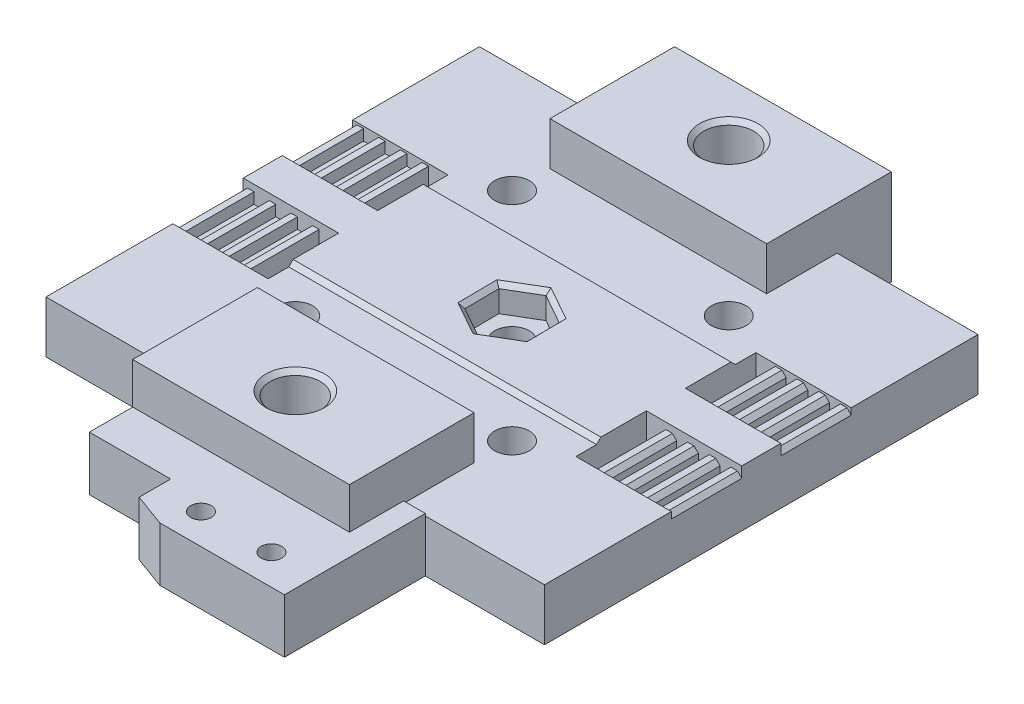
SolidWorks part; units mm, degrees
ref_plane "前视基准面" through (0, 0, 0) normal (0, 0, 1) x (1, 0, 0)
ref_plane "上视基准面" through (0, 0, 0) normal (0, 1, 0) x (1, 0, 0)
ref_plane "右视基准面" through (0, 0, 0) normal (1, 0, 0) x (0, 0, -1)
other "Configuration Table"
sketch "草图1" plane through (0, 0, 0) normal (0, 1, 0) x (1, 0, 0)
  line L1 (0, 0) -> (40, 0)
  line L2 (0, 0) -> (0, -40)
  line L3 (0, -40) -> (40, -40)
  line L4 (40, 0) -> (40, -40)
  dimension "D1" = 40
  dimension "40" = 40
extrude "凸台-拉伸1" add sketch "草图1" along normal blind 4.8
sketch "草图2" plane through (0, 4.8, 0) normal (0, 1, 0) x (1, 0, 0)
  line L0 (0, -40) -> (40, -40) construction
  line L1 (0, 0) -> (0, -40) construction
  circle A0 centre (10, -30) radius 1.6
  circle A1 centre (30, -30) radius 1.6
  circle A2 centre (30, -10) radius 1.6
  circle A3 centre (10, -10) radius 1.6
  dimension "D1" = 3.2
  dimension "D4" = 10
  dimension "D5" = 10
  dimension "D2" = 2
  dimension "D3" = 2
extrude "切除-拉伸1" cut sketch "草图2" against normal through all
sketch "草图3" plane through (0, 4.8, 0) normal (0, 1, 0) x (1, 0, 0)
  line L0 (0, 0) -> (0, -40) construction
  line L1 (0, -13.6) -> (40, -13.6)
  line L2 (0, -13.6) -> (0, -26.4)
  line L3 (0, -26.4) -> (40, -26.4)
  line L4 (40, -13.6) -> (40, -26.4)
  line L5 (40, -40) -> (40, 0) construction
  line L6 (40, 0) -> (0, 0) construction
  dimension "D1" = 12.8
  dimension "D2" = 13.6
extrude "凸台-拉伸2" add sketch "草图3" along normal blind 0.4
chamfer "倒角1" distance 0.4 angle 45 2 edges at (20, 5.2, 26.4) (20, 5.2, 13.6)
sketch "草图4" plane through (0, 0, 0) normal (0, -1, 0) x (1, 0, 0)
  line L0 (0, 40) -> (40, 40) construction
  line L1 (10, 40) -> (30, 40)
  line L2 (10, 40) -> (10, 45)
  line L3 (10, 45) -> (30, 45)
  line L4 (30, 40) -> (30, 45)
  line L5 (40, 0) -> (0, 0) construction
  line L6 (10, 0) -> (30, 0)
  line L7 (10, 0) -> (10, -5)
  line L8 (10, -5) -> (30, -5)
  line L9 (30, 0) -> (30, -5)
  line L10 (40, 40) -> (40, 0) construction
  point P12 (20, 0)
  point P15 (20, 40)
  dimension "D1" = 20
  dimension "D2" = 20
  dimension "D3" = 20
  dimension "D4" = 20
  dimension "D5" = 5
  dimension "D6" = 5
extrude "凸台-拉伸3" add sketch "草图4" against normal blind 4.8
sketch "草图5" plane through (0, 0, 0) normal (0, -1, 0) x (-1, 0, 0)
  line L0 (0, 0) -> (0, -40) construction
  line L1 (-30, -40) -> (-40, -40) construction
  circle A0 centre (-20, -20) radius 1.6
  circle A1 centre (-20, 0) radius 1.6
  circle A2 centre (-20, -40) radius 1.6
  dimension "D1" = 3.2
  dimension "D2" = 3.2
  dimension "D3" = 3.2
  dimension "D4" = 20
  dimension "D5" = 20
  dimension "D6" = 20
  dimension "D7" = 20
  dimension "D8" = 20
  dimension "D9" = 20
extrude "切除-拉伸2" cut sketch "草图5" against normal through all
sketch "草图6" plane through (0, 0, 0) normal (0, -1, 0) x (-1, 0, 0)
  line L0 (-30, -45) -> (-10, -45) construction
  line L1 (-15.5, -45) -> (-24.5, -45)
  line L2 (-15.5, -45) -> (-15.5, 5)
  line L3 (-15.5, 5) -> (-24.5, 5)
  line L4 (-24.5, -45) -> (-24.5, 5)
  line L5 (-10, 5) -> (-30, 5) construction
  line L6 (-30, -40) -> (-30, -45) construction
  point P8 (-20, -45)
  dimension "D1" = 9
  dimension "D2" = 10
extrude "切除-拉伸4" cut sketch "草图6" against normal blind 0.8
sketch "草图7" plane through (0, 4.8, 0) normal (0, 1, 0) x (1, 0, 0)
  line L0 (0, 0) -> (0, -13.6) construction
  line L1 (0, -6.5) -> (40, -6.5) construction
  line L2 (0, -6.5) -> (0, -33.5) construction
  line L3 (0, -33.5) -> (40, -33.5) construction
  line L4 (40, -6.5) -> (40, -33.5) construction
  line L5 (40, -40) -> (40, -26.4) construction
  line L6 (0, -40) -> (10, -40) construction
  line L8 (10, 5) -> (30, 5)
  line L9 (10, 5) -> (10, -6.5)
  line L10 (10, -6.5) -> (30, -6.5)
  line L11 (30, 5) -> (30, -6.5)
  line L12 (10, -45) -> (30, -45)
  line L13 (10, -45) -> (10, -33.5)
  line L14 (10, -33.5) -> (30, -33.5)
  line L15 (30, -45) -> (30, -33.5)
  circle A0 centre (20, 0) radius 1.6
  circle A1 centre (20, -40) radius 1.6
  point P8 (0, -20)
  dimension "D1" = 27
  dimension "D2" = 20
extrude "凸台-拉伸4" add sketch "草图7" along normal blind 4
sketch "草图8" plane through (0, 8.8, 0) normal (0, 1, 0) x (1, 0, 0)
  circle A0 centre (20, 0) radius 2.3
  circle A1 centre (20, -40) radius 2.3
  dimension "D1" = 4.6
  dimension "D2" = 4.6
extrude "切除-拉伸5" cut sketch "草图8" against normal blind 4.4
chamfer "倒角2" distance 0.4 angle 45 2 edges at (20, 8.8, 42.3) (20, 8.8, 2.3)
sketch "草图9" plane through (0, 5.2, 0) normal (0, 1, 0) x (1, 0, 0)
  line L1 (22.7676, -21.5568) -> (22.732, -18.3816)
  line L2 (22.732, -18.3816) -> (19.9644, -16.8248)
  line L3 (19.9644, -16.8248) -> (17.2324, -18.4432)
  line L4 (17.2324, -18.4432) -> (17.268, -21.6184)
  line L5 (17.268, -21.6184) -> (20.0356, -23.1752)
  line L6 (20.0356, -23.1752) -> (22.7676, -21.5568)
  circle A0 centre (20, -20) radius 2.75 construction
  dimension "D1" = 5.5
extrude "切除-拉伸6" cut sketch "草图9" against normal blind 2.4
chamfer "倒角3" distance 0.4 angle 45 6 edges at (21.3482, 5.2, 17.6032) (22.7498, 5.2, 19.9692) (21.4016, 5.2, 22.366) (18.6518, 5.2, 22.3968) (17.2502, 5.2, 20.0308) (18.5984, 5.2, 17.634)
sketch "草图10" plane through (40, 0, 0) normal (1, 0, 0) x (0, 0, -1)
  line L16 (-14, 5.2) -> (-26, 5.2)
  line L17 (-26, 5.2) -> (-26.4, 4.8)
  line L18 (-26.4, 4.8) -> (-40, 4.8)
  line L19 (-40, 4.8) -> (-40, 0)
  line L20 (-40, 0) -> (0, 0)
  line L21 (0, 0) -> (0, 4.8)
  line L22 (0, 4.8) -> (-13.6, 4.8)
  line L23 (-13.6, 4.8) -> (-14, 5.2)
  line L24 (-14, 5.2) -> (-26, 5.2)
  line L25 (-26, 5.2) -> (-26.4, 4.8)
  line L26 (-26.4, 4.8) -> (-40, 4.8)
  line L27 (-40, 4.8) -> (-40, 0)
  line L28 (-40, 0) -> (0, 0)
  line L29 (0, 0) -> (0, 4.8)
  line L30 (0, 4.8) -> (-13.6, 4.8)
  line L31 (-13.6, 4.8) -> (-14, 5.2)
  dimension "D1" = 0
extrude "凸台-拉伸5" add sketch "草图10" along normal blind 3
sketch "草图11" plane through (0, 0, 0) normal (-1, 0, 0) x (0, 0, 1)
  line L16 (40, 4.8) -> (26.4, 4.8)
  line L17 (26.4, 4.8) -> (26, 5.2)
  line L18 (26, 5.2) -> (14, 5.2)
  line L19 (14, 5.2) -> (13.6, 4.8)
  line L20 (13.6, 4.8) -> (0, 4.8)
  line L21 (0, 4.8) -> (0, 0)
  line L22 (0, 0) -> (40, 0)
  line L23 (40, 0) -> (40, 4.8)
  line L24 (40, 4.8) -> (26.4, 4.8)
  line L25 (26.4, 4.8) -> (26, 5.2)
  line L26 (26, 5.2) -> (14, 5.2)
  line L27 (14, 5.2) -> (13.6, 4.8)
  line L28 (13.6, 4.8) -> (0, 4.8)
  line L29 (0, 4.8) -> (0, 0)
  line L30 (0, 0) -> (40, 0)
  line L31 (40, 0) -> (40, 4.8)
  dimension "D1" = 0
extrude "凸台-拉伸6" add sketch "草图11" along normal blind 3
sketch "草图12" plane through (0, 0, 0) normal (0, -1, 0) x (-1, 0, 0)
  line L0 (3, 0) -> (3, -40) construction
  line L1 (3, -28.3) -> (-6.3, -28.3) construction
  line L2 (3, -28.3) -> (3, -21.8) construction
  line L3 (3, -21.8) -> (-6.3, -21.8) construction
  line L4 (-6.3, -28.3) -> (-6.3, -21.8) construction
  line L5 (0, -28.3) -> (0, -21.8)
  line L6 (3, -18.2) -> (-6.3, -18.2) construction
  line L7 (3, -18.2) -> (3, -11.7) construction
  line L8 (3, -11.7) -> (-6.3, -11.7) construction
  line L9 (-6.3, -18.2) -> (-6.3, -11.7) construction
  line L10 (3, -40) -> (-10, -40) construction
  line L11 (0, -28.3) -> (-1, -28.3)
  line L12 (-20, -45) -> (-20, -4.7094) construction
  line L13 (-24.5, 5) -> (-24.5, -45) construction
  line L14 (-1, -28.3) -> (-1, -21.8)
  line L15 (-43, -11.7) -> (-33.7, -11.7) construction
  line L16 (-33.7, -18.2) -> (-33.7, -11.7) construction
  line L17 (-43, -18.2) -> (-43, -11.7) construction
  line L18 (-43, -28.3) -> (-43, -21.8) construction
  line L19 (-43, -21.8) -> (-33.7, -21.8) construction
  line L20 (-33.7, -28.3) -> (-33.7, -21.8) construction
  line L21 (-43, -28.3) -> (-33.7, -28.3) construction
  line L22 (-33.7, -18.2) -> (-43, -18.2) construction
  line L23 (0, -21.8) -> (-1, -21.8)
  line L24 (2, -28.3) -> (1, -28.3)
  line L25 (2, -28.3) -> (2, -21.8)
  line L26 (2, -21.8) -> (1, -21.8)
  line L27 (1, -28.3) -> (1, -21.8)
  line L28 (-2, -28.3) -> (-2, -21.8)
  line L29 (-2, -28.3) -> (-3, -28.3)
  line L30 (-3, -28.3) -> (-3, -21.8)
  line L31 (-2, -21.8) -> (-3, -21.8)
  line L32 (-4, -28.3) -> (-4, -21.8)
  line L33 (-4, -28.3) -> (-5, -28.3)
  line L34 (-5, -28.3) -> (-5, -21.8)
  line L35 (-4, -21.8) -> (-5, -21.8)
  line L36 (3, -20) -> (-12.765, -20) construction
  line L37 (-4, -11.7) -> (-5, -11.7)
  line L38 (-5, -11.7) -> (-5, -18.2)
  line L39 (-4, -18.2) -> (-5, -18.2)
  line L40 (-4, -11.7) -> (-4, -18.2)
  line L41 (-2, -11.7) -> (-3, -11.7)
  line L42 (-3, -11.7) -> (-3, -18.2)
  line L43 (-2, -18.2) -> (-3, -18.2)
  line L44 (-2, -11.7) -> (-2, -18.2)
  line L45 (0, -11.7) -> (-1, -11.7)
  line L46 (-1, -11.7) -> (-1, -18.2)
  line L47 (0, -18.2) -> (-1, -18.2)
  line L48 (0, -11.7) -> (0, -18.2)
  line L49 (2, -18.2) -> (1, -18.2)
  line L50 (1, -11.7) -> (1, -18.2)
  line L51 (2, -11.7) -> (1, -11.7)
  line L52 (2, -11.7) -> (2, -18.2)
  line L53 (-36, -11.7) -> (-36, -18.2)
  line L54 (-36, -18.2) -> (-35, -18.2)
  line L55 (-35, -11.7) -> (-35, -18.2)
  line L56 (-36, -11.7) -> (-35, -11.7)
  line L57 (-38, -11.7) -> (-38, -18.2)
  line L58 (-38, -18.2) -> (-37, -18.2)
  line L59 (-37, -11.7) -> (-37, -18.2)
  line L60 (-38, -11.7) -> (-37, -11.7)
  line L61 (-40, -11.7) -> (-40, -18.2)
  line L62 (-40, -18.2) -> (-39, -18.2)
  line L63 (-39, -11.7) -> (-39, -18.2)
  line L64 (-40, -11.7) -> (-39, -11.7)
  line L65 (-42, -11.7) -> (-42, -18.2)
  line L66 (-42, -11.7) -> (-41, -11.7)
  line L67 (-41, -11.7) -> (-41, -18.2)
  line L68 (-42, -18.2) -> (-41, -18.2)
  line L69 (-36, -28.3) -> (-35, -28.3)
  line L70 (-35, -28.3) -> (-35, -21.8)
  line L71 (-36, -21.8) -> (-35, -21.8)
  line L72 (-36, -28.3) -> (-36, -21.8)
  line L73 (-38, -28.3) -> (-37, -28.3)
  line L74 (-37, -28.3) -> (-37, -21.8)
  line L75 (-38, -21.8) -> (-37, -21.8)
  line L76 (-38, -28.3) -> (-38, -21.8)
  line L77 (-40, -28.3) -> (-39, -28.3)
  line L78 (-39, -28.3) -> (-39, -21.8)
  line L79 (-40, -21.8) -> (-39, -21.8)
  line L80 (-40, -28.3) -> (-40, -21.8)
  line L81 (-42, -21.8) -> (-41, -21.8)
  line L82 (-41, -28.3) -> (-41, -21.8)
  line L83 (-42, -28.3) -> (-41, -28.3)
  line L84 (-42, -28.3) -> (-42, -21.8)
  dimension "D1" = 6.5
  dimension "D2" = 3.6
  dimension "D3" = 6.5
  dimension "D4" = 9.3
  dimension "D5" = 9.3
  dimension "D6" = 11.7
  dimension "D7" = 4.5
  dimension "D8" = 1
  dimension "D9" = 1
  dimension "D10" = 4
extrude "切除-拉伸7" cut sketch "草图12" against normal blind 1
sketch "草图13" plane through (0, 0, 0) normal (0, -1, 0) x (-1, 0, 0)
  line L1 (-4, -28.3) -> (-5.8, -28.3)
  line L2 (-4, -28.3) -> (-4, -21.8)
  line L3 (-4, -21.8) -> (-5.8, -21.8)
  line L4 (-5.8, -28.3) -> (-5.8, -21.8)
  line L5 (-4, -18.2) -> (-5.8, -18.2)
  line L6 (-4, -18.2) -> (-4, -11.7)
  line L7 (-4, -11.7) -> (-5.8, -11.7)
  line L8 (-5.8, -18.2) -> (-5.8, -11.7)
  line L9 (-36, -28.3) -> (-34.2, -28.3)
  line L10 (-36, -28.3) -> (-36, -21.8)
  line L11 (-36, -21.8) -> (-34.2, -21.8)
  line L12 (-34.2, -28.3) -> (-34.2, -21.8)
  line L13 (-36, -18.2) -> (-34.2, -18.2)
  line L14 (-36, -18.2) -> (-36, -11.7)
  line L15 (-36, -11.7) -> (-34.2, -11.7)
  line L16 (-34.2, -18.2) -> (-34.2, -11.7)
  dimension "D1" = 1.8
  dimension "D2" = 1.8
  dimension "D3" = 1.8
  dimension "D4" = 1.8
extrude "切除-拉伸8" cut sketch "草图13" against normal through all
sketch "草图14" plane through (0, 5.2, 0) normal (0, 1, 0) x (1, 0, 0)
  line L0 (-3, -26) -> (-3, -14) construction
  line L1 (5.8, -11.7) -> (-3, -11.7)
  line L2 (5.8, -11.7) -> (5.8, -18.2)
  line L3 (5.8, -18.2) -> (-3, -18.2)
  line L4 (-3, -11.7) -> (-3, -18.2)
  line L5 (-3, -40) -> (-3, -26.4) construction
  line L6 (5.8, -21.8) -> (-3, -21.8)
  line L7 (5.8, -21.8) -> (5.8, -28.3)
  line L8 (5.8, -28.3) -> (-3, -28.3)
  line L9 (-3, -21.8) -> (-3, -28.3)
  line L10 (43, -14) -> (43, -26) construction
  line L11 (34.2, -11.7) -> (43, -11.7)
  line L12 (34.2, -11.7) -> (34.2, -18.2)
  line L13 (34.2, -18.2) -> (43, -18.2)
  line L14 (43, -11.7) -> (43, -18.2)
  line L15 (43, -26.4) -> (43, -40) construction
  line L16 (34.2, -21.8) -> (43, -21.8)
  line L17 (34.2, -21.8) -> (34.2, -28.3)
  line L18 (34.2, -28.3) -> (43, -28.3)
  line L19 (43, -21.8) -> (43, -28.3)
extrude "切除-拉伸9" cut sketch "草图14" against normal blind 0.6
sketch "草图15" plane through (0, 4.6, 0) normal (0, 1, 0) x (1, 0, 0)
  line L0 (4, -11.7) -> (-3, -11.7) construction
  line L1 (-2, -11.7) -> (-1, -11.7)
  line L2 (-2, -11.7) -> (-2, -18.2)
  line L3 (-2, -18.2) -> (-1, -18.2)
  line L4 (-1, -11.7) -> (-1, -18.2)
  line L5 (-3, -18.2) -> (5.8, -18.2) construction
  line L6 (-3, -11.7) -> (-3, -18.2) construction
  line L7 (0, -11.7) -> (0, -18.2)
  line L8 (0, -11.7) -> (1, -11.7)
  line L9 (1, -11.7) -> (1, -18.2)
  line L10 (0, -18.2) -> (1, -18.2)
  line L11 (2, -11.7) -> (2, -18.2)
  line L12 (2, -11.7) -> (3, -11.7)
  line L13 (3, -11.7) -> (3, -18.2)
  line L14 (2, -18.2) -> (3, -18.2)
  line L15 (-3, -20) -> (11.9387, -20) construction
  line L16 (-3, -21.8) -> (-3, -18.2) construction
  line L17 (2, -28.3) -> (3, -28.3)
  line L18 (3, -28.3) -> (3, -21.8)
  line L19 (2, -21.8) -> (3, -21.8)
  line L20 (2, -28.3) -> (2, -21.8)
  line L21 (0, -28.3) -> (1, -28.3)
  line L22 (1, -28.3) -> (1, -21.8)
  line L23 (0, -21.8) -> (1, -21.8)
  line L24 (0, -28.3) -> (0, -21.8)
  line L25 (-2, -21.8) -> (-1, -21.8)
  line L26 (-1, -28.3) -> (-1, -21.8)
  line L27 (-2, -28.3) -> (-1, -28.3)
  line L28 (-2, -28.3) -> (-2, -21.8)
  line L29 (20, 5) -> (20, -11.7) construction
  line L30 (30, 5) -> (10, 5) construction
  line L31 (42, -28.3) -> (42, -21.8)
  line L32 (42, -28.3) -> (41, -28.3)
  line L33 (41, -28.3) -> (41, -21.8)
  line L34 (42, -21.8) -> (41, -21.8)
  line L35 (40, -28.3) -> (40, -21.8)
  line L36 (40, -21.8) -> (39, -21.8)
  line L37 (39, -28.3) -> (39, -21.8)
  line L38 (40, -28.3) -> (39, -28.3)
  line L39 (38, -28.3) -> (38, -21.8)
  line L40 (38, -21.8) -> (37, -21.8)
  line L41 (37, -28.3) -> (37, -21.8)
  line L42 (38, -28.3) -> (37, -28.3)
  line L43 (38, -11.7) -> (37, -11.7)
  line L44 (37, -11.7) -> (37, -18.2)
  line L45 (38, -18.2) -> (37, -18.2)
  line L46 (38, -11.7) -> (38, -18.2)
  line L47 (40, -11.7) -> (39, -11.7)
  line L48 (39, -11.7) -> (39, -18.2)
  line L49 (40, -18.2) -> (39, -18.2)
  line L50 (40, -11.7) -> (40, -18.2)
  line L51 (42, -18.2) -> (41, -18.2)
  line L52 (41, -11.7) -> (41, -18.2)
  line L53 (42, -11.7) -> (41, -11.7)
  line L54 (42, -11.7) -> (42, -18.2)
  dimension "D1" = 1
  dimension "D2" = 1
  dimension "D3" = 3
extrude "切除-拉伸10" cut sketch "草图15" against normal blind 1
sketch "草图16" plane through (0, 0, 45) normal (0, 0, 1) x (1, 0, 0)
  line L0 (10, 4.8) -> (10, 0) construction
  line L1 (30, 0) -> (10, 0)
  line L2 (30, 0) -> (30, 5)
  line L3 (30, 5) -> (10, 5)
  line L4 (10, 0) -> (10, 5)
  dimension "D1" = 0
  dimension "D2" = 5
extrude "凸台-拉伸7" add sketch "草图16" along normal blind 8
sketch "草图17" plane through (0, 0, 0) normal (0, -1, 0) x (-1, 0, 0)
  line L0 (-10, -53) -> (-30, -53) construction
  line L2 (-30, -40) -> (-30, -53) construction
  circle A0 centre (-21.5, -50.2) radius 0.95
  circle A1 centre (-28, -50.2) radius 0.95
  point P6 (-27.9133, -53)
  point P9 (-30, -48.4687)
  dimension "D1" = 1.9
  dimension "D2" = 1.9
  dimension "D4" = 2.8
  dimension "D5" = 2
  dimension "D6" = 6.5
  dimension "D3" = 2.8
extrude "切除-拉伸11" cut sketch "草图17" against normal through all
sketch "草图18" plane through (0, 5, 0) normal (0, 1, 0) x (1, 0, 0)
  line L0 (30, -53) -> (10, -53) construction
  line L1 (10, -53) -> (17.5, -53)
  line L2 (10, -53) -> (10, -49)
  line L3 (10, -49) -> (17.5, -49)
  line L4 (17.5, -53) -> (17.5, -49)
  dimension "D1" = 7.5
  dimension "D2" = 4
extrude "切除-拉伸12" cut sketch "草图18" against normal through all
sketch "草图19" plane through (30, 0, 0) normal (1, 0, 0) x (0, 0, -1)
  line L0 (-40, 4.8) -> (-40, 0) construction
  line L1 (-53, 5) -> (-40, 5)
  line L2 (-53, 5) -> (-53, 0)
  line L3 (-53, 0) -> (-40, 0)
  line L4 (-40, 5) -> (-40, 0)
  line L5 (-40, 0) -> (-53, 0) construction
extrude "凸台-拉伸8" add sketch "草图19" along normal blind 2
chamfer "倒角4" distance 3 angle 20 1 edges at (17.5, 2.5, 53) first distance on face at (24.75, 2.5, 53)
sketch "草图20" plane through (0, 0, 0) normal (0, -1, 0) x (-1, 0, 0)
  line L0 (-15.5, -45) -> (-24.5, -45) construction
  line L1 (-16, -44.5) -> (-24, -44.5)
  line L2 (-16, -44.5) -> (-16, 4.5)
  line L3 (-16, 4.5) -> (-24, 4.5)
  line L4 (-24, -44.5) -> (-24, 4.5)
  line L5 (-24.5, 5) -> (-24.5, -45) construction
  line L6 (-15.5, -45) -> (-15.5, 5) construction
  line L7 (-15.5, 5) -> (-24.5, 5) construction
  dimension "D1" = 0.5
  dimension "D2" = 0.5
  dimension "D3" = 0.5
  dimension "D4" = 0.5
extrude "凸台-拉伸9" add sketch "草图20" against normal blind 0.6 separate body
sketch "草图21" plane through (0, 0, -4.5) normal (0, 0, -1) x (-1, 0, 0)
  line L0 (-16, 0.6) -> (-24, 0.6) construction
  line L1 (-23.2, 0.6) -> (-22.4, 0.6)
  line L2 (-23.2, 0.6) -> (-23.2, 0.4)
  line L3 (-23.2, 0.4) -> (-22.4, 0.4)
  line L4 (-22.4, 0.6) -> (-22.4, 0.4)
  line L5 (-24, 0.6) -> (-24, 0) construction
  line L6 (-16, 0) -> (-24, 0) construction
  line L7 (-21.5434, 0.6) -> (-21.5434, 0.4)
  line L8 (-21.5434, 0.6) -> (-20.7434, 0.6)
  line L9 (-20.7434, 0.6) -> (-20.7434, 0.4)
  line L10 (-21.5434, 0.4) -> (-20.7434, 0.4)
  line L11 (-19.8868, 0.6) -> (-19.8868, 0.4)
  line L12 (-19.8868, 0.6) -> (-19.0868, 0.6)
  line L13 (-19.0868, 0.6) -> (-19.0868, 0.4)
  line L14 (-19.8868, 0.4) -> (-19.0868, 0.4)
  line L15 (-18.2302, 0.6) -> (-18.2302, 0.4)
  line L16 (-18.2302, 0.6) -> (-17.4302, 0.6)
  line L17 (-17.4302, 0.6) -> (-17.4302, 0.4)
  line L18 (-18.2302, 0.4) -> (-17.4302, 0.4)
  line L20 (-17.0302, 0.6) -> (-16.6302, 0.6)
  line L21 (-17.0302, 0.6) -> (-17.0302, 0.4)
  line L22 (-17.0302, 0.4) -> (-16.6302, 0.4)
  line L23 (-16.6302, 0.6) -> (-16.6302, 0.4)
  dimension "D1" = 0.8
  dimension "D2" = 0.8
  dimension "D3" = 0.4
  dimension "D5" = 0.4
  dimension "D6" = 0.4
  dimension "D4" = 4
extrude "切除-拉伸13" cut sketch "草图21" against normal blind 49
chamfer "倒角5" distance 0.4 angle 45 16 edges at (-2, 0, 25.05) (0, 0, 25.05) (2, 0, 25.05) (4, 0, 25.05) (4, 0, 14.95) (2, 0, 14.95) (0, 0, 14.95) (-2, 0, 14.95) (36, 0, 25.05) (38, 0, 25.05) (40, 0, 25.05) (42, 0, 25.05) (36, 0, 14.95) (38, 0, 14.95) (42, 0, 14.95) (40, 0, 14.95)
chamfer "倒角6" distance 0.4 angle 45 16 edges at (3, 4.6, 14.95) (1, 4.6, 14.95) (-1, 4.6, 14.95) (-3, 4.6, 14.95) (-3, 4.6, 25.05) (-1, 4.6, 25.05) (1, 4.6, 25.05) (3, 4.6, 25.05) (39, 4.6, 14.95) (37, 4.6, 14.95) (37, 4.6, 25.05) (39, 4.6, 25.05) (41, 4.6, 25.05) (41, 4.6, 14.95) (43, 4.6, 14.95) (43, 4.6, 25.05)
equation "\"D2@草图3\"=20-6.4"
equation "\"D6@草图12\"=20-6.5-1.8"
